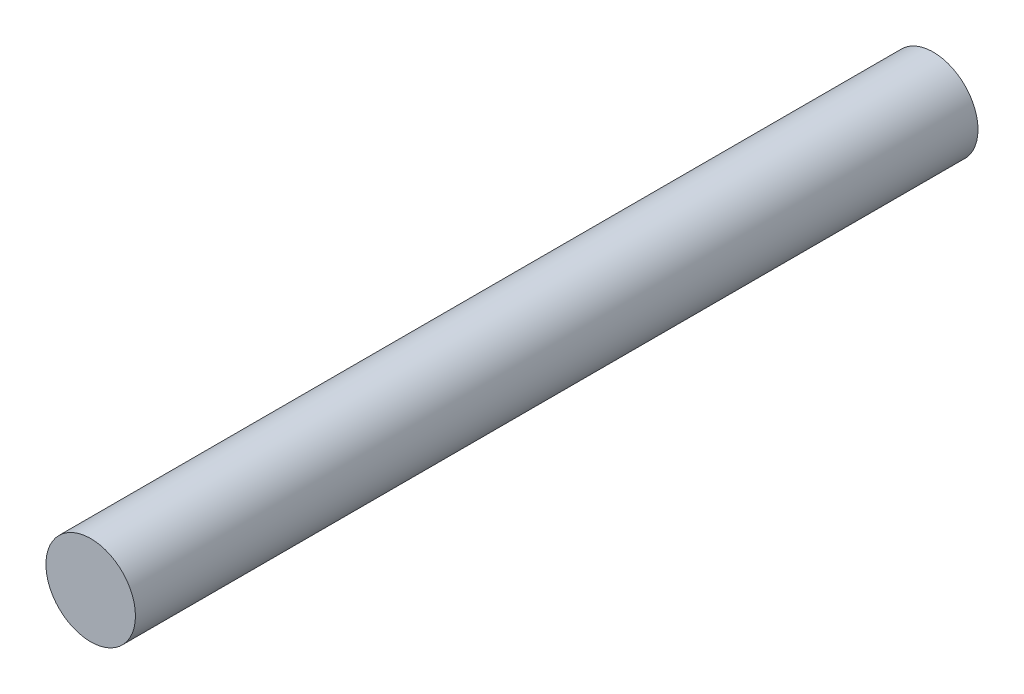
SolidWorks part; units mm, degrees
ref_plane "Alzado" through (0, 0, 0) normal (0, 0, 1) x (1, 0, 0)
ref_plane "Planta" through (0, 0, 0) normal (0, 1, 0) x (1, 0, 0)
ref_plane "Vista lateral" through (0, 0, 0) normal (1, 0, 0) x (0, 0, -1)
sketch "Croquis1" plane through (0, 0, 0) normal (0, 0, 1) x (1, 0, 0)
  circle A0 centre (0, 0) radius 10.795
  dimension "D1" = 21.59
extrude "Saliente-Extruir1" add sketch "Croquis1" along normal blind 203.2
